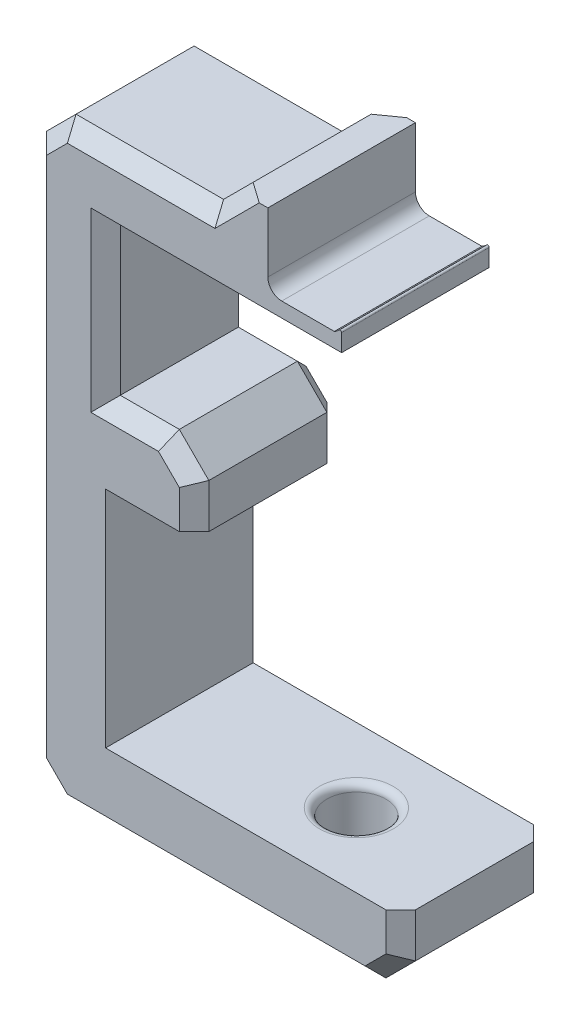
SolidWorks part; units mm, degrees
ref_plane "Plano frontal" through (0, 0, 0) normal (0, 0, 1) x (1, 0, 0)
ref_plane "Plano superior" through (0, 0, 0) normal (0, 1, 0) x (1, 0, 0)
ref_plane "Plano direito" through (0, 0, 0) normal (1, 0, 0) x (0, 0, -1)
sketch "Esboço1" plane through (0, 0, 0) normal (0, 0, 1) x (1, 0, 0)
  line L0 (11, 14.25) -> (-5, 14.25)
  line L1 (1, -0.75) -> (-5, -0.75)
  line L2 (-5, 14.25) -> (-5, 4.25)
  line L3 (-5, -15.95) -> (15, -15.95)
  line L4 (15, -15.95) -> (15, -20.95)
  line L5 (15, -20.95) -> (-10, -20.95)
  line L6 (-10, -20.95) -> (-10, 19.25)
  line L7 (1, 4.25) -> (1, -0.75)
  line L8 (1, 4.25) -> (-5, 4.25)
  line L9 (-5, -0.75) -> (-5, -15.95)
  line L10 (11, 14.25) -> (11, 16.25)
  line L11 (10.5044, 16.25) -> (6, 16.25)
  line L12 (6, 16.25) -> (6, 19.25)
  line L13 (6, 19.25) -> (-10, 19.25)
  line L14 (11, 16.25) -> (11, 16.4263)
  arc A0 (11, 16.4263) -> (10.8262, 16.4939) centre (10.9, 16.4263) ccw
  arc A1 (10.5044, 16.25) -> (10.8262, 16.4939) centre (10, 17.25) ccw
  dimension "D12" = 0.1
  dimension "D1" = 5
  dimension "D2" = 20
  dimension "D3" = 15.2
  dimension "D4" = 6
  dimension "D5" = 5
  dimension "D6" = 5
  dimension "D7" = 2
  dimension "D8" = 5
  dimension "D9" = 10
  dimension "D10" = 16
  dimension "D11" = 5
  dimension "D13" = 0.1763
  dimension "D14" = 0.4956
extrude "Ressalto-extrusão1" add sketch "Esboço1" along normal blind 10
sketch "Esboço3" plane through (0, -20.95, 0) normal (0, -1, 0) x (1, 0, 0)
  line L0 (15, 5) -> (7, 5) construction
  line L1 (15, 10) -> (15, 0) construction
  circle A0 centre (7, 5) radius 2
  dimension "D1" = 4
  dimension "D2" = 8
extrude "Corte-extrusão1" cut sketch "Esboço3" against normal blind 15
chamfer "Chanfro1" distance 1.6 angle 45 1 edges at (7, -20.95, 3)
fillet "Filete1" radius 0.5 1 edges at (7, -15.95, 3)
fillet "Filete2" radius 0.94 1 edges at (6, 16.25, 5)
sketch "Esboço5" plane through (0, 0, 10) normal (0, 0, 1) x (1, 0, 0)
  line L0 (6, 19.25) -> (6, 21.25)
  line L1 (6, 21.25) -> (4, 21.25)
  line L2 (4, 21.25) -> (2, 19.25)
  line L3 (6, 19.25) -> (-10, 19.25) construction
  line L4 (2, 19.25) -> (6, 19.25)
  dimension "D1" = 135
  dimension "D2" = 2
  dimension "D3" = 2
extrude "Ressalto-extrusão3" add sketch "Esboço5" against normal up to surface (10 mm away) up to face at (3.1829, 4.8624, 0)
chamfer "Chanfro5" distance 2 angle 45 4 edges at (15, -20.95, 5) (-10, -20.95, 5) (-10, 19.25, 5) (1, 4.25, 5)
chamfer "Chanfro4" distance 1 angle 45 27 edges at (-5, 9.25, 0) (-5, 9.25, 10) (3, 14.25, 0) (3, 14.25, 10) (11, 14.25, 5) (-3, 4.25, 0) (-3, 4.25, 10) (3, 20.25, 0) (-3, 19.25, 0) (-9, 18.25, 0) (-10, -0.85, 0) (-9, -19.95, 0) (2.5, -20.95, 0) (14, -19.95, 0) (15, -17.45, 0) (3, 20.25, 10) (-3, 19.25, 10) (-9, 18.25, 10) (-10, -0.85, 10) (-9, -19.95, 10) (2.5, -20.95, 10) (14, -19.95, 10) (15, -17.45, 10) (1, 0.75, 10) (0, 3.25, 10) (1, 0.75, 0) (0, 3.25, 0)
